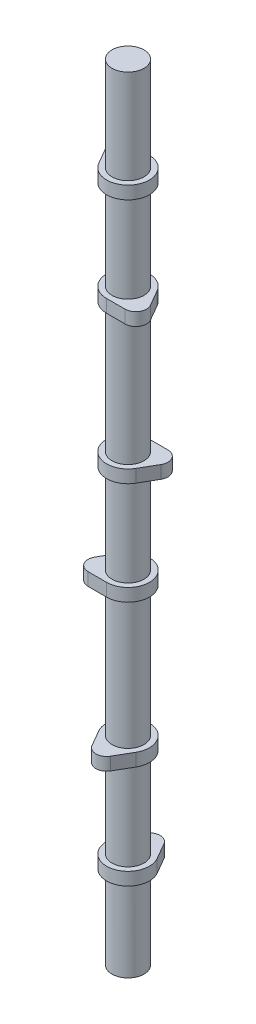
SolidWorks part; units mm, degrees
material "Plain Carbon Steel"
ref_plane "Front Plane" through (0, 0, 0) normal (0, 0, 1) x (1, 0, 0)
ref_plane "Top Plane" through (0, 0, 0) normal (0, 1, 0) x (1, 0, 0)
ref_plane "Right Plane" through (0, 0, 0) normal (1, 0, 0) x (0, 0, -1)
sketch "Sketch1" plane through (0, 0, 0) normal (0, 1, 0) x (1, 0, 0)
  line L0 (0, -443.5475) -> (0, 443.5475) construction
  line L1 (-139.6812, 403.225) -> (-279.3625, 161.29)
  line L2 (139.6812, 403.225) -> (279.3625, 161.29)
  arc A0 (-279.3625, 161.29) -> (279.3625, 161.29) centre (0, 0) ccw
  arc A1 (139.6812, 403.225) -> (-139.6812, 403.225) centre (0, 322.58) ccw
extrude "Boss-Extrude1" add sketch "Sketch1" along normal mid plane 193.548
ref_axis "Axis1" through (0, 11613.7687, 0) along (0, -1, 0)
move or copy body "Body-Move/Copy1" bodies to move or copy 101 copy yes number of copies 1 translate (0, 1548.384, 0)
move or copy body "Body-Move/Copy2" bodies to move or copy 102 copy no rotation origin (0, 0, 0) rotation axis (0, 1, 0) rotation angle 180
sketch "Sketch3" plane through (0, 0, 0) normal (0, 1, 0) x (1, 0, 0)
  circle A0 centre (0, 0) radius 241.3
extrude "Boss-Extrude2" add sketch "Sketch3" along normal blind 3709.67 from offset 645.16 offset against normal yes
pattern_linear "LPattern1" count 3 spacing 3709.67 along (0, 1, 0) of bodies 104
move or copy body "Body-Move/Copy3" bodies to move or copy 105 copy no rotation origin (0, 0, 0) rotation axis (0, 1, 0) rotation angle 120
move or copy body "Body-Move/Copy4" bodies to move or copy 106 copy no rotation origin (0, 0, 0) rotation axis (0, -1, 0) rotation angle 120
sketch "Sketch4" plane through (0, -645.16, 0) normal (0, -1, 0) x (1, 0, 0)
  circle A1 centre (0, 0) radius 241.3
  circle A2 centre (0, 0) radius 241.3
  dimension "D1" = 0
extrude "Boss-Extrude3" add sketch "Sketch4" along normal blind 709.676
combine bodies "Combine1" operation type add bodies to combine 109 107 108
scale "Scale1" scale about centroid uniform scaling yes scale factor 0.03937
ref_plane "Plane1" through (0, 4377.3851, 0) normal (0, -1, 0) x (-1, 0, 0)
